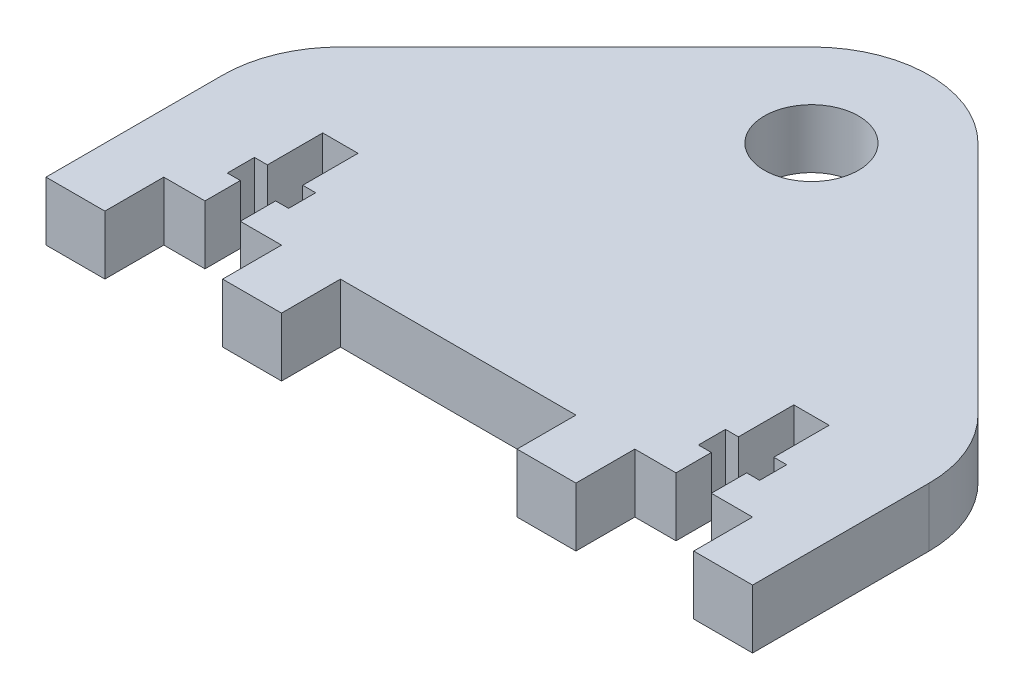
SolidWorks part; units mm, degrees
ref_plane "Front Plane" through (0, 0, 0) normal (0, 0, 1) x (1, 0, 0)
ref_plane "Top Plane" through (0, 0, 0) normal (0, 1, 0) x (1, 0, 0)
ref_plane "Right Plane" through (0, 0, 0) normal (1, 0, 0) x (0, 0, -1)
sketch "Sketch1" plane through (0, 0, 0) normal (0, 1, 0) x (1, 0, 0)
  line L1 (-30, 10) -> (-30, -5)
  line L2 (-30, -5) -> (-25, -5)
  line L3 (-10, -5) -> (-10, 0)
  line L4 (-10, 0) -> (10, 0)
  line L5 (10, -5) -> (10, 0)
  line L6 (30, -5) -> (25, -5)
  line L7 (30, 10) -> (30, -5)
  line L11 (0, 0) -> (0, 43.6328) construction
  line L13 (-27.0711, 17.0711) -> (-7.0711, 37.0711)
  line L14 (7.0711, 37.0711) -> (27.0711, 17.0711)
  line L36 (-25, -5) -> (-25, 0)
  line L37 (-25, 0) -> (-21.5, 0)
  line L38 (-21.5, 0) -> (-21.5, 3)
  line L39 (-21.5, 3) -> (-22.6, 3)
  line L40 (-22.6, 3) -> (-22.6, 5.3)
  line L41 (-22.6, 5.3) -> (-21.5, 5.3)
  line L42 (-21.5, 5.3) -> (-21.5, 10)
  line L43 (-21.5, 10) -> (-18.5, 10)
  line L44 (-18.5, 10) -> (-18.5, 5.3)
  line L45 (-18.5, 5.3) -> (-17.4, 5.3)
  line L46 (-17.4, 5.3) -> (-17.4, 3)
  line L47 (-17.4, 3) -> (-18.5, 3)
  line L48 (-18.5, 3) -> (-18.5, 0)
  line L49 (-18.5, 0) -> (-15, 0)
  line L50 (-15, 0) -> (-15, -5)
  line L51 (-15, -5) -> (-10, -5)
  line L52 (25, 0) -> (21.5, 0)
  line L53 (21.5, 0) -> (21.5, 3)
  line L54 (21.5, 3) -> (22.6, 3)
  line L55 (22.6, 5.3) -> (21.5, 5.3)
  line L56 (22.6, 3) -> (22.6, 5.3)
  line L57 (21.5, 5.3) -> (21.5, 10)
  line L58 (21.5, 10) -> (18.5, 10)
  line L59 (18.5, 10) -> (18.5, 5.3)
  line L60 (18.5, 5.3) -> (17.4, 5.3)
  line L61 (17.4, 5.3) -> (17.4, 3)
  line L62 (17.4, 3) -> (18.5, 3)
  line L63 (18.5, 3) -> (18.5, 0)
  line L64 (18.5, 0) -> (15, 0)
  line L65 (15, 0) -> (15, -5)
  line L66 (25, -5) -> (25, 0)
  line L67 (15, -5) -> (10, -5)
  arc A0 (-7.0711, 37.0711) -> (7.0711, 37.0711) centre (0, 30) cw
  circle A2 centre (0, 30) radius 4
  arc A3 (30, 10) -> (27.0711, 17.0711) centre (20, 10) ccw
  arc A4 (-30, 10) -> (-27.0711, 17.0711) centre (-20, 10) cw
  circle A7 centre (0, 30) radius 30 construction
  circle A8 centre (0, 30) radius 23.5 construction
  point P68 (-16.75, 0)
  point P72 (-17.95, 3)
  point P73 (-22.05, 5.3)
  point P74 (-22.05, 3)
  point P78 (22.05, 3)
  point P80 (22.05, 5.3)
  point P88 (17.95, 3)
  point P91 (16.75, 0)
  dimension "D1" = 4
  dimension "D4" = 10
  dimension "D6" = 60
  dimension "D8" = 60
  dimension "D3" = 10
  dimension "D9" = 47
  dimension "D2" = 5
  dimension "D5" = 10
  dimension "D7" = 10
  dimension "D12" = 5
  dimension "D13" = 5
  dimension "D15" = 2.3
  dimension "D16" = 3
  dimension "D17" = 10
  dimension "D18" = 3
  dimension "D19" = 3.5
  dimension "D20" = 5.2
  dimension "D21" = 2.6
extrude "Boss-Extrude1" add sketch "Sketch1" along normal blind 5
